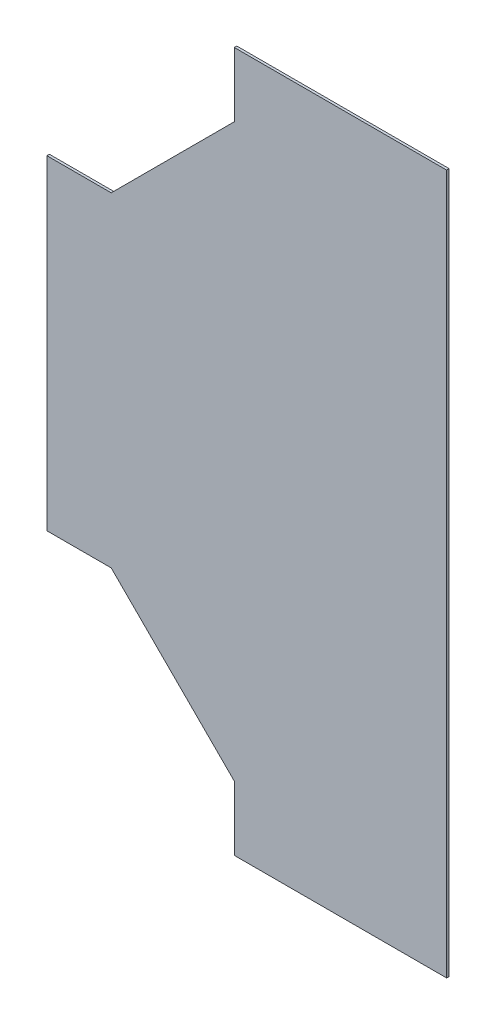
SolidWorks part; units mm, degrees
ref_plane "Front Plane" through (0, 0, 0) normal (1, 0, 0) x (0, 1, 0)
ref_plane "Top Plane" through (0, 0, 0) normal (0, 0, 1) x (0, 1, 0)
ref_plane "Right Plane" through (0, 0, 0) normal (0, 1, 0) x (-1, 0, 0)
sketch "Sketch1" plane through (0, 0, 0) normal (0, 0, 1) x (0, 1, 0)
  line L1 (-355.6, -203.2) -> (355.6, -203.2)
  line L2 (-355.6, -203.2) -> (-355.6, 203.2)
  line L3 (-355.6, 203.2) -> (355.6, 203.2)
  line L4 (355.6, -203.2) -> (355.6, 203.2)
  line L5 (-355.6, -203.2) -> (355.6, 203.2) construction
  line L6 (-355.6, 203.2) -> (355.6, -203.2) construction
  point P0 (0, 0)
  dimension "D1" = 711.2
  dimension "D2" = 406.4
extrude "Boss-Extrude1" add sketch "Sketch1" along normal blind 2.54
sketch "Sketch2" plane through (0, 0, 2.54) normal (0, 0, 1) x (1, 0, 0)
  line L0 (-203.2, 165.1) -> (-12.7, 165.1) construction
  line L1 (-203.2, 355.6) -> (-203.2, -355.6) construction
  line L2 (-12.7, 165.1) -> (-12.7, 355.6) construction
  line L3 (203.2, 355.6) -> (-203.2, 355.6) construction
  line L4 (-137.7627, 165.1) -> (-12.7, 290.1627)
  line L5 (-12.7, 355.6) -> (-12.7, 290.1627)
  line L6 (-137.7627, 165.1) -> (-203.2, 165.1)
  line L7 (-203.2, 0) -> (203.2, 0) construction
  line L8 (203.2, -355.6) -> (203.2, 355.6) construction
  line L9 (-12.7, 355.6) -> (-203.2, 355.6)
  line L10 (-203.2, 355.6) -> (-203.2, 165.1)
  line L11 (-12.7, -355.6) -> (-203.2, -355.6)
  line L12 (-12.7, -355.6) -> (-12.7, -290.1627)
  line L13 (-137.7627, -165.1) -> (-12.7, -290.1627)
  line L14 (-137.7627, -165.1) -> (-203.2, -165.1)
  line L15 (-203.2, -355.6) -> (-203.2, -165.1)
  dimension "D1" = 190.5
  dimension "D2" = 45
  dimension "D3" = 180.975
extrude "Cut-Extrude1" cut sketch "Sketch2" against normal through all
